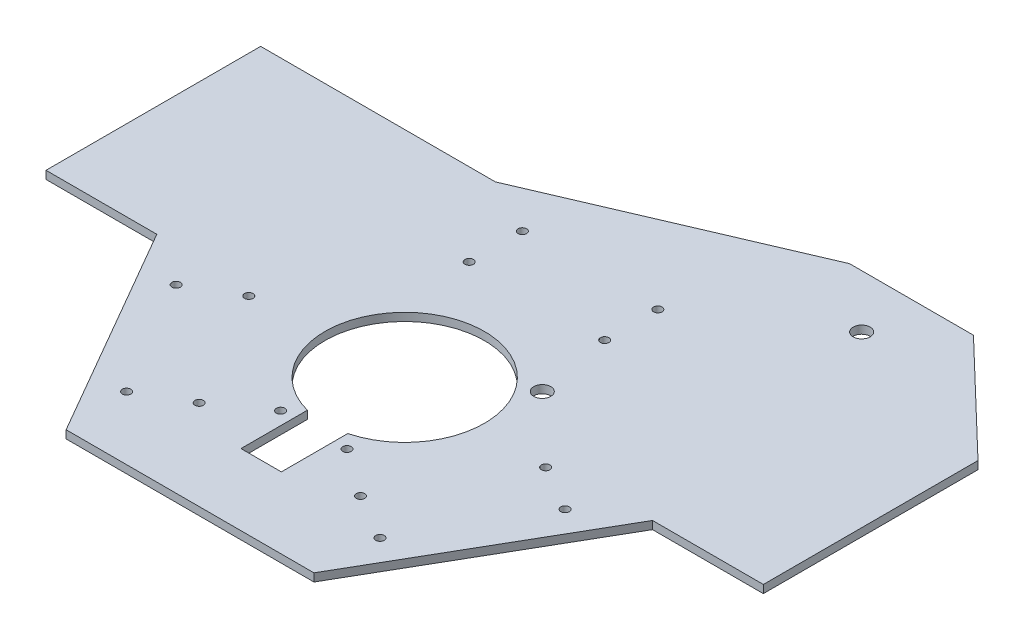
SolidWorks part; units mm, degrees
material "Carbon Fiber"
ref_plane "Front Plane" through (0, 0, 0) normal (0, 0, 1) x (1, 0, 0)
ref_plane "Top Plane" through (0, 0, 0) normal (0, 1, 0) x (1, 0, 0)
ref_plane "Right Plane" through (0, 0, 0) normal (1, 0, 0) x (0, 0, -1)
sketch "Sketch1" plane through (0, 0, 0) normal (0, 1, 0) x (1, 0, 0)
  line L0 (0, 0) -> (0, 59.7887) construction
  line L1 (88.7366, -45.4586) -> (19.8205, -5.6699) construction
  line L2 (-5, 99.5775) -> (5, 99.5775) construction
  line L3 (-5, 99.5775) -> (-5, 20) construction
  line L4 (-5, 20) -> (5, 20) construction
  line L5 (5, 99.5775) -> (5, 20) construction
  line L6 (-5, 99.5775) -> (5, 20) construction
  line L7 (-5, 20) -> (5, 99.5775) construction
  line L8 (88.7366, -45.4586) -> (83.7366, -54.1189) construction
  line L9 (83.7366, -54.1189) -> (14.8205, -14.3301) construction
  line L10 (19.8205, -5.6699) -> (14.8205, -14.3301) construction
  line L11 (-83.7366, -54.1189) -> (-14.8205, -14.3301) construction
  line L12 (-83.7366, -54.1189) -> (-88.7366, -45.4586) construction
  line L13 (-88.7366, -45.4586) -> (-19.8205, -5.6699) construction
  line L14 (-14.8205, -14.3301) -> (-19.8205, -5.6699) construction
  line L15 (-5, 59.7887) -> (-120, 59.7887) construction
  line L16 (-49.2786, -34.2245) -> (8.2214, -133.8174) construction
  line L23 (54.2786, -25.5642) -> (111.7786, 74.0287) construction
  circle A0 centre (0, 0) radius 20 construction
  circle A1 centre (-12.5, -19.3067) radius 3 construction
  circle A2 centre (12.5, -19.3067) radius 3 construction
  point P19 (0, 0)
  dimension "D1" = 40
  dimension "D6" = 6
  dimension "D7" = 25
  dimension "D2" = 79.5775
  dimension "D3" = 10
  dimension "D5" = 115
  dimension "D4" = 3
sketch "Sketch2" plane through (0, 0, 0) normal (0, 1, 0) x (1, 0, 0)
  line L0 (-5, 20) -> (5, 99.5775) construction
  line L1 (-25.5, 49.7887) -> (25.5, 49.7887) construction
  line L2 (-25.5, 49.7887) -> (-25.5, 69.7887) construction
  line L3 (-25.5, 69.7887) -> (25.5, 69.7887) construction
  line L4 (25.5, 49.7887) -> (25.5, 69.7887) construction
  line L5 (-25.5, 49.7887) -> (25.5, 69.7887) construction
  line L6 (-25.5, 69.7887) -> (25.5, 49.7887) construction
  line L8 (46.6434, 80.7887) -> (-46.6434, 80.7887)
  line L9 (-46.6434, 80.7887) -> (-93.2868, 0)
  line L10 (-93.2868, 0) -> (-46.6434, -80.7887)
  line L11 (-46.6434, -80.7887) -> (46.6434, -80.7887)
  line L12 (46.6434, -80.7887) -> (93.2868, 0)
  line L13 (93.2868, 0) -> (46.6434, 80.7887)
  circle A0 centre (25.5, 69.7887) radius 1.6
  circle A1 centre (25.5, 49.7887) radius 1.6
  circle A2 centre (-25.5, 49.7887) radius 1.6
  circle A3 centre (-25.5, 69.7887) radius 1.6
  circle A4 centre (0, 0) radius 30
  circle A5 centre (0, 0) radius 80.7887 construction
  circle A6 centre (55.8683, -2.8107) radius 1.6
  circle A7 centre (73.1888, -12.8107) radius 1.6
  circle A8 centre (47.6888, -56.978) radius 1.6
  circle A9 centre (30.3683, -46.978) radius 1.6
  circle A10 centre (-30.3683, -46.978) radius 1.6
  circle A11 centre (-47.6888, -56.978) radius 1.6
  circle A12 centre (-73.1888, -12.8107) radius 1.6
  circle A13 centre (-55.8683, -2.8107) radius 1.6
  point P0 (0, 59.7887)
  point P39 (0, 0)
  dimension "D3" = 3.2
  dimension "D4" = 60
  dimension "D5" = 11
  dimension "D1" = 51
  dimension "D2" = 20
  dimension "D6" = 3
extrude "Boss-Extrude1" add sketch "Sketch2" along normal blind 3
sketch "Sketch3" plane through (0, 0, 0) normal (0, 1, 0) x (1, 0, 0)
  line L0 (18, 80.7887) -> (18, 24) construction
  line L1 (46.6434, 80.7887) -> (-46.6434, 80.7887) construction
  line L2 (5, 99.5775) -> (5, 20) construction
  line L3 (85.9256, 92.2887) -> (41.3253, 15.0387) construction
  line L5 (25.5, 49.7887) -> (30.5, 49.7887) construction
  line L6 (30.5, 33.7887) -> (30.5, 49.7887) construction
  line L8 (46.6434, 120.7887) -> (93.2868, 120.7887)
  line L9 (93.2868, 120.7887) -> (93.2868, 0)
  line L14 (93.2868, 0) -> (46.6434, 80.7887) construction
  line L15 (93.2868, 0) -> (46.6434, 80.7887)
  line L16 (-46.6434, 80.7887) -> (46.6434, 120.7887)
  line L17 (46.6434, 120.7887) -> (46.6434, 80.7887) construction
  line L18 (46.6434, 80.7887) -> (-46.6434, 80.7887)
  line L19 (46.6434, -80.7887) -> (93.2868, 0) construction
  circle A0 centre (0, 0) radius 30 construction
  circle A1 centre (30.5, 21.2887) radius 12.5 construction
  circle A5 centre (71.2032, 100.7887) radius 3.2
  circle A6 centre (71.2032, 100.7887) radius 20 construction
  circle A7 centre (71.2032, 100.7887) radius 17 construction
  point P19 (85.9256, 92.2887)
  point P32 (69.9651, 120.7887)
  dimension "D2" = 25
  dimension "D3" = 16
  dimension "D4" = 6.4
  dimension "D5" = 20
  dimension "D6" = 34
  dimension "D1" = 13
extrude "Boss-Extrude2" add sketch "Sketch3" along normal up to surface (3 mm away) up to face at (-30.3683, 3, 48.578)
sketch "Sketch4" plane through (0, 3, 0) normal (0, 1, 0) x (1, 0, 0)
  circle A0 centre (30.5, 21.2887) radius 3.2
  dimension "D1" = 6.4
extrude "Cut-Extrude1" cut sketch "Sketch4" against normal through all
sketch "Sketch5" plane through (0, 3, 0) normal (0, 1, 0) x (1, 0, 0)
  line L4 (-7.6, -29.0214) -> (7.6, -29.0214)
  line L5 (-7.6, -29.0214) -> (-7.6, -54.0214)
  line L6 (-7.6, -54.0214) -> (7.6, -54.0214)
  line L7 (7.6, -29.0214) -> (7.6, -54.0214)
  circle A2 centre (0, 0) radius 30 construction
  dimension "D1" = 15.2
  dimension "D2" = 25
extrude "Cut-Extrude2" cut sketch "Sketch5" against normal through all
sketch "Sketch7" plane through (0, 0, 0) normal (0, -1, 0) x (1, 0, 0)
  line L0 (0, 0) -> (0, 34.2214) construction
  line L1 (0, 34.2214) -> (12.5, 34.2214) construction
  line L2 (0, 34.2214) -> (-12.5, 34.2214) construction
  circle A0 centre (-12.5, 34.2214) radius 1.6
  circle A1 centre (12.5, 34.2214) radius 1.6
  dimension "D1" = 25
  dimension "D3" = 3.2
  dimension "D2" = 34.2214
extrude "Cut-Extrude3" cut sketch "Sketch7" against normal through all
sketch "Sketch8" plane through (0, 0, 0) normal (0, 1, 0) x (1, 0, 0)
  line L0 (-93.2868, 0) -> (-135, 0)
  line L1 (-135, 0) -> (-135, 80.7887)
  line L2 (-135, 80.7887) -> (-46.6434, 80.7887)
  line L3 (-93.2868, 0) -> (-46.6434, 80.7887)
  line L4 (93.2868, 0) -> (135, 0)
  line L5 (135, 0) -> (135, 80.7887)
  line L6 (135, 80.7887) -> (93.2868, 120.7887)
  line L7 (93.2868, 0) -> (93.2868, 120.7887)
  dimension "D1" = 270
extrude "Boss-Extrude3" add sketch "Sketch8" along normal up to surface (3 mm away) up to face at (-12.5, 3, 32.6214)
